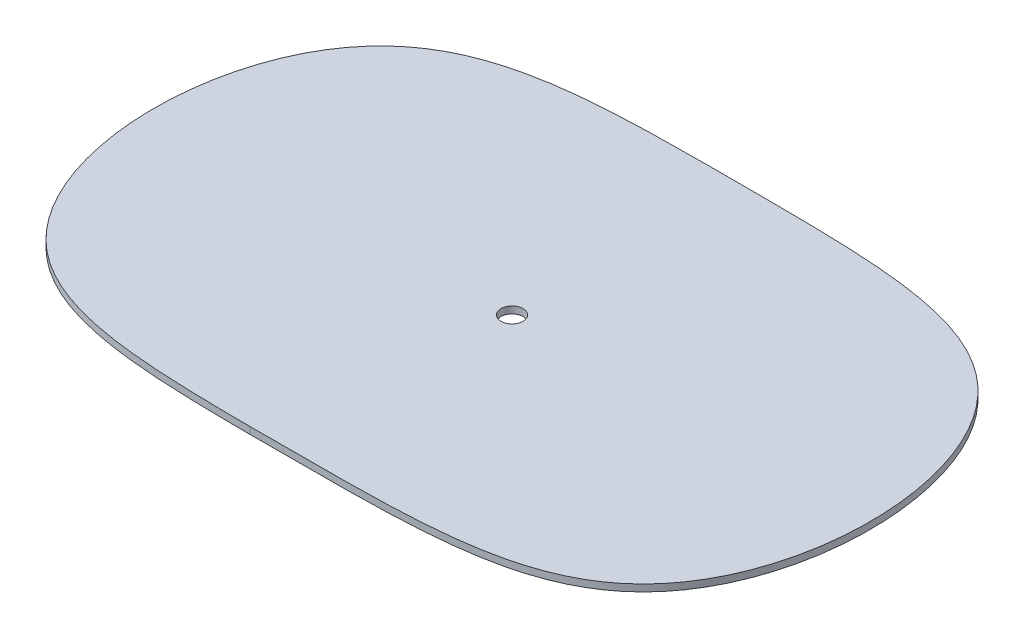
SolidWorks part; units mm, degrees
ref_plane "Front Plane" through (0, 0, 0) normal (0, 0, 1) x (1, 0, 0)
ref_plane "Top Plane" through (0, 0, 0) normal (0, 1, 0) x (1, 0, 0)
ref_plane "Right Plane" through (0, 0, 0) normal (1, 0, 0) x (0, 0, -1)
sketch "Sketch1" plane through (0, 0, 0) normal (0, 1, 0) x (1, 0, 0)
  spline S6 degree 3 poles (-30, 99.067) (-32.5327, 99.056) (-37.6133, 99.0256) (-47.6531, 98.9126) (-60.0179, 98.6321) (-74.4127, 97.9094) (-92.831, 96.1793) (-109.7176, 92.8756) (-124.2868, 87.3897) (-133.9756, 82.1249) (-142.4887, 75.6313) (-152.4064, 65.232) (-162.1821, 48.8712) (-169.2895, 25.3202) (-171.6409, 0) (-169.2894, -25.3203) (-162.1823, -48.8709) (-152.4062, -65.2323) (-142.4881, -75.632) (-133.9764, -82.1239) (-124.2878, -87.3898) (-109.7139, -92.8764) (-92.8309, -96.1792) (-74.4132, -97.9094) (-60.0176, -98.6321) (-47.6532, -98.9125) (-37.6131, -99.0256) (-32.5327, -99.0561) (-30, -99.067) knots 0.054313 0.054313 0.054313 0.054313 0.068241 0.082169 0.110024 0.13788 0.165735 0.221446 0.249301 0.277157 0.305012 0.332868 0.388578 0.444289 0.5 0.555711 0.611422 0.667132 0.694988 0.722843 0.750699 0.778554 0.834265 0.86212 0.889976 0.917831 0.931759 0.945687 0.945687 0.945687 0.945687
  spline S7 degree 3 poles (-30, -99.067) (-24.2315, -99.067) (-12.666, -99.07) (10.2362, -99.0235) (38.1343, -98.5942) (63.9239, -96.1449) (82.2489, -91.8582) (94.5593, -87.2939) (105.3056, -81.2744) (114.5883, -73.7) (122.545, -64.4514) (131.372, -49.9523) (138.8298, -28.4026) (141.787, 0.0011) (138.8292, 28.4049) (131.3715, 49.9535) (122.5434, 64.4534) (111.9365, 76.7831) (98.6609, 85.7728) (82.2491, 91.858) (63.9205, 96.1458) (38.1314, 98.5941) (10.2347, 99.0235) (-12.6706, 99.0698) (-24.2327, 99.0675) (-30, 99.067) knots -0.000005 -0.000005 -0.000005 -0.000005 0.031245 0.062495 0.124995 0.187496 0.218746 0.249996 0.281246 0.312496 0.343747 0.374997 0.437497 0.499997 0.562498 0.624998 0.656248 0.687498 0.749999 0.781249 0.812499 0.874999 0.9375 0.96875 1 1 1 1
extrude "Boss-Extrude1" add sketch "Sketch1" along normal blind 3
sketch "Sketch2" plane through (0, 0, 0) normal (0, 1, 0) x (1, 0, 0)
  circle A0 centre (-15.028, 0) radius 4.8
  dimension "D1" = 9.6
extrude "Cut-Extrude1" cut sketch "Sketch2" along normal through all
